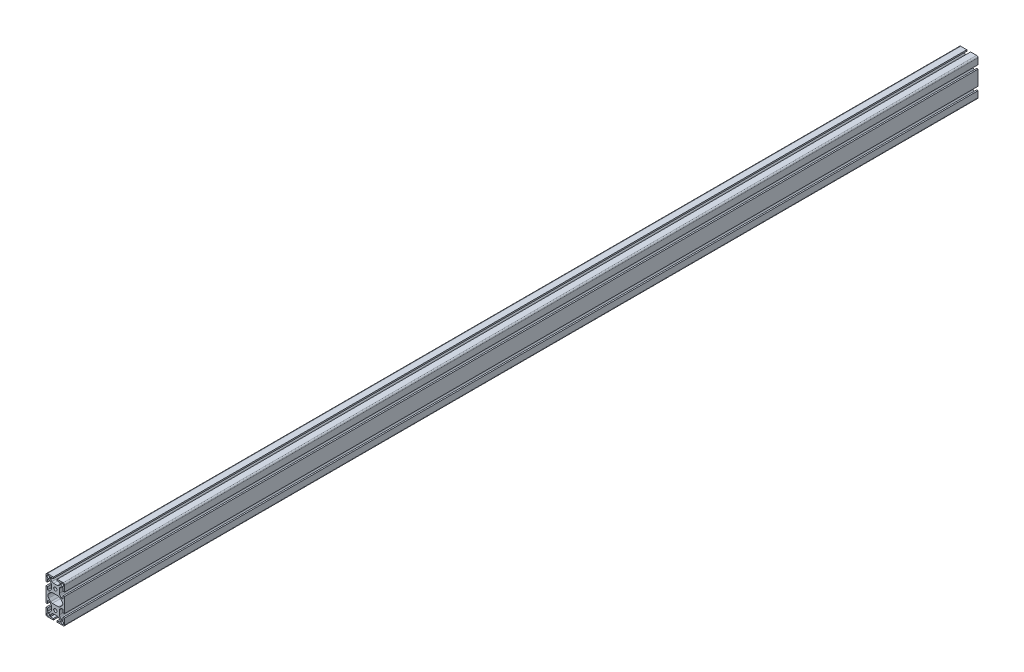
SolidWorks part; units mm, degrees
ref_plane "Front Plane" through (0, 0, 0) normal (0, 0, 1) x (1, 0, 0)
ref_plane "Top Plane" through (0, 0, 0) normal (0, 1, 0) x (1, 0, 0)
ref_plane "Right Plane" through (0, 0, 0) normal (1, 0, 0) x (0, 0, -1)
sketch "Sketch1" plane through (0, 0, 0) normal (0, 0, 1) x (1, 0, 0)
  line L0 (-17, -40) -> (-4.1, -40)
  line L1 (-4.1, -40) -> (-4.1, -37)
  line L2 (-4.1, -37) -> (-10.5, -37)
  line L3 (-10.5, -37) -> (-10.5, -33.6627)
  line L4 (-10.0314, -32.5314) -> (-7.4645, -29.9645)
  line L5 (-3.9289, -28.5) -> (3.9289, -28.5)
  line L6 (7.4645, -29.9645) -> (10.0314, -32.5314)
  line L7 (10.5, -33.6627) -> (10.5, -37)
  line L8 (10.5, -37) -> (4.1, -37)
  line L9 (4.1, -37) -> (4.1, -40)
  line L10 (4.1, -40) -> (17, -40)
  line L11 (20, -37) -> (20, -24.1)
  line L12 (20, -24.1) -> (17, -24.1)
  line L13 (17, -24.1) -> (17, -30.5)
  line L14 (17, -30.5) -> (13.6627, -30.5)
  line L15 (12.5314, -30.0314) -> (9.9645, -27.4645)
  line L16 (8.5, -23.9289) -> (8.5, -16.0711)
  line L17 (9.9645, -12.5355) -> (12.5314, -9.9686)
  line L18 (13.6627, -9.5) -> (17, -9.5)
  line L19 (17, -9.5) -> (17, -15.9)
  line L20 (17, -15.9) -> (20, -15.9)
  line L21 (20, -15.9) -> (20, 15.9)
  line L22 (20, 15.9) -> (17, 15.9)
  line L23 (17, 15.9) -> (17, 9.5)
  line L24 (17, 9.5) -> (13.6627, 9.5)
  line L25 (12.5314, 9.9686) -> (9.9645, 12.5355)
  line L26 (8.5, 16.0711) -> (8.5, 23.9289)
  line L27 (9.9645, 27.4645) -> (12.5314, 30.0314)
  line L28 (13.6627, 30.5) -> (17, 30.5)
  line L29 (17, 30.5) -> (17, 24.1)
  line L30 (17, 24.1) -> (20, 24.1)
  line L31 (20, 24.1) -> (20, 37)
  line L32 (17, 40) -> (4.1, 40)
  line L33 (4.1, 40) -> (4.1, 37)
  line L34 (4.1, 37) -> (10.5, 37)
  line L35 (10.5, 37) -> (10.5, 33.6627)
  line L36 (10.0314, 32.5314) -> (7.4645, 29.9645)
  line L37 (3.9289, 28.5) -> (-3.9289, 28.5)
  line L38 (-7.4645, 29.9645) -> (-10.0314, 32.5314)
  line L39 (-10.5, 33.6627) -> (-10.5, 37)
  line L40 (-10.5, 37) -> (-4.1, 37)
  line L41 (-4.1, 37) -> (-4.1, 40)
  line L42 (-4.1, 40) -> (-17, 40)
  line L43 (-20, 37) -> (-20, 24.1)
  line L44 (-20, 24.1) -> (-17, 24.1)
  line L45 (-17, 24.1) -> (-17, 30.5)
  line L46 (-17, 30.5) -> (-13.6627, 30.5)
  line L47 (-12.5314, 30.0314) -> (-9.9645, 27.4645)
  line L48 (-8.5, 23.9289) -> (-8.5, 16.0711)
  line L49 (-9.9645, 12.5355) -> (-12.5314, 9.9686)
  line L50 (-13.6627, 9.5) -> (-17, 9.5)
  line L51 (-17, 9.5) -> (-17, 15.9)
  line L52 (-17, 15.9) -> (-20, 15.9)
  line L53 (-20, 15.9) -> (-20, -15.9)
  line L54 (-20, -15.9) -> (-17, -15.9)
  line L55 (-17, -15.9) -> (-17, -9.5)
  line L56 (-17, -9.5) -> (-13.6627, -9.5)
  line L57 (-12.5314, -9.9686) -> (-9.9645, -12.5355)
  line L58 (-8.5, -16.0711) -> (-8.5, -23.9289)
  line L59 (-9.9645, -27.4645) -> (-12.5314, -30.0314)
  line L60 (-13.6627, -30.5) -> (-17, -30.5)
  line L61 (-17, -30.5) -> (-17, -24.1)
  line L62 (-17, -24.1) -> (-20, -24.1)
  line L63 (-20, -24.1) -> (-20, -37)
  line L64 (-14.2426, -4.2426) -> (-9.9497, -8.5355)
  line L65 (-6.4142, -10) -> (6.4142, -10)
  line L66 (9.9497, -8.5355) -> (14.2426, -4.2426)
  line L67 (14.2426, 4.2426) -> (9.9497, 8.5355)
  line L68 (6.4142, 10) -> (-6.4142, 10)
  line L69 (-9.9497, 8.5355) -> (-14.2426, 4.2426)
  arc A0 (-20, -37) -> (-17, -40) centre (-17, -37) ccw
  arc A1 (-10.5, -33.6627) -> (-10.0314, -32.5314) centre (-8.9, -33.6627) cw
  arc A2 (-7.4645, -29.9645) -> (-3.9289, -28.5) centre (-3.9289, -33.5) cw
  arc A3 (3.9289, -28.5) -> (7.4645, -29.9645) centre (3.9289, -33.5) cw
  arc A4 (10.0314, -32.5314) -> (10.5, -33.6627) centre (8.9, -33.6627) cw
  arc A5 (17, -40) -> (20, -37) centre (17, -37) ccw
  arc A6 (13.6627, -30.5) -> (12.5314, -30.0314) centre (13.6627, -28.9) cw
  arc A7 (9.9645, -27.4645) -> (8.5, -23.9289) centre (13.5, -23.9289) cw
  arc A8 (8.5, -16.0711) -> (9.9645, -12.5355) centre (13.5, -16.0711) cw
  arc A9 (12.5314, -9.9686) -> (13.6627, -9.5) centre (13.6627, -11.1) cw
  arc A10 (13.6627, 9.5) -> (12.5314, 9.9686) centre (13.6627, 11.1) cw
  arc A11 (9.9645, 12.5355) -> (8.5, 16.0711) centre (13.5, 16.0711) cw
  arc A12 (8.5, 23.9289) -> (9.9645, 27.4645) centre (13.5, 23.9289) cw
  arc A13 (12.5314, 30.0314) -> (13.6627, 30.5) centre (13.6627, 28.9) cw
  arc A14 (20, 37) -> (17, 40) centre (17, 37) ccw
  arc A15 (10.5, 33.6627) -> (10.0314, 32.5314) centre (8.9, 33.6627) cw
  arc A16 (7.4645, 29.9645) -> (3.9289, 28.5) centre (3.9289, 33.5) cw
  arc A17 (-3.9289, 28.5) -> (-7.4645, 29.9645) centre (-3.9289, 33.5) cw
  arc A18 (-10.0314, 32.5314) -> (-10.5, 33.6627) centre (-8.9, 33.6627) cw
  arc A19 (-17, 40) -> (-20, 37) centre (-17, 37) ccw
  arc A20 (-13.6627, 30.5) -> (-12.5314, 30.0314) centre (-13.6627, 28.9) cw
  arc A21 (-9.9645, 27.4645) -> (-8.5, 23.9289) centre (-13.5, 23.9289) cw
  arc A22 (-8.5, 16.0711) -> (-9.9645, 12.5355) centre (-13.5, 16.0711) cw
  arc A23 (-12.5314, 9.9686) -> (-13.6627, 9.5) centre (-13.6627, 11.1) cw
  arc A24 (-13.6627, -9.5) -> (-12.5314, -9.9686) centre (-13.6627, -11.1) cw
  arc A25 (-9.9645, -12.5355) -> (-8.5, -16.0711) centre (-13.5, -16.0711) cw
  arc A26 (-8.5, -23.9289) -> (-9.9645, -27.4645) centre (-13.5, -23.9289) cw
  arc A27 (-12.5314, -30.0314) -> (-13.6627, -30.5) centre (-13.6627, -28.9) cw
  circle A28 centre (15, 35) radius 3
  circle A29 centre (15, -35) radius 3
  circle A30 centre (0, 20) radius 3.5
  circle A31 centre (0, -20) radius 3.5
  arc A32 (-14.2426, 4.2426) -> (-14.2426, -4.2426) centre (-10, 0) ccw
  arc A33 (-9.9497, -8.5355) -> (-6.4142, -10) centre (-6.4142, -5) ccw
  arc A34 (6.4142, -10) -> (9.9497, -8.5355) centre (6.4142, -5) ccw
  arc A35 (14.2426, -4.2426) -> (14.2426, 4.2426) centre (10, 0) ccw
  arc A36 (9.9497, 8.5355) -> (6.4142, 10) centre (6.4142, 5) ccw
  arc A37 (-6.4142, 10) -> (-9.9497, 8.5355) centre (-6.4142, 5) ccw
  circle A38 centre (-15, 35) radius 3
  circle A39 centre (-15, -35) radius 3
  dimension "D3" = 6
  dimension "D4" = 6
  dimension "D5" = 6
  dimension "D6" = 6
  dimension "D7" = 7
  dimension "D8" = 7
  dimension "D1" = 40
  dimension "D2" = 80
extrude "Boss-Extrude1" add sketch "Sketch1" against normal blind 1961
